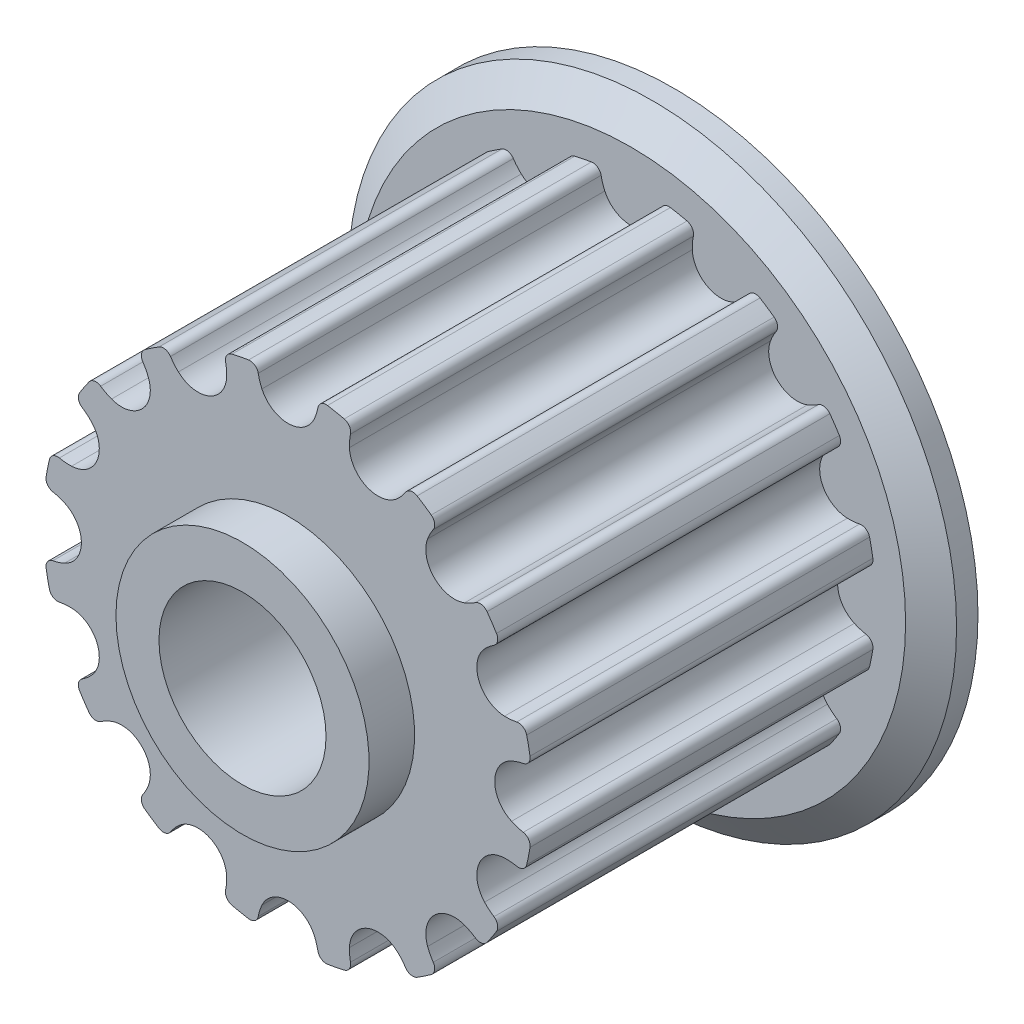
SolidWorks part; units mm, degrees
ref_plane "Front Plane" through (0, 0, 0) normal (0, 0, 1) x (1, 0, 0)
ref_plane "Top Plane" through (0, 0, 0) normal (0, 1, 0) x (1, 0, 0)
ref_plane "Right Plane" through (0, 0, 0) normal (1, 0, 0) x (0, 0, -1)
sketch "Sketch1" plane through (0, 0, 0) normal (0, 0, 1) x (1, 0, 0)
  line L1 (-2.553, 6.1245) -> (2.553, 6.1245) construction
  line L4 (0, 0) -> (0, 6.1245) construction
  line L5 (0, 6.1245) -> (0, 12.0665) construction
  line L6 (0, 7.6455) -> (2.9417, 7.0569) construction
  line L7 (2.9417, 7.0569) -> (3.8741, 6.6682) construction
  line L8 (2.9417, 7.0569) -> (2.553, 6.1245) construction
  line L9 (-2.9417, 7.0569) -> (-2.553, 6.1245) construction
  line L10 (-2.7951, 6.7052) -> (-3.7579, 9.015)
  line L11 (-3.7579, 9.015) -> (3.7579, 9.015)
  line L12 (3.7579, 9.015) -> (2.7951, 6.7052)
  circle A0 centre (0, 0) radius 7.6455 construction
  circle A1 centre (0, 0) radius 9.015 construction
  circle A2 centre (0, 0) radius 7.2645 construction
  arc A3 (-0.7739, 6.6229) -> (0.7739, 6.6229) centre (0, 6.9745) ccw
  arc A4 (-0.7739, 6.6229) -> (-0.8836, 6.9694) centre (0.61, 7.2516) cw
  arc A5 (-2.7951, 6.7052) -> (-1.1695, 7.1697) centre (0, 0) cw
  arc A6 (-0.8836, 6.9694) -> (-1.1695, 7.1697) centre (-1.1292, 6.923) ccw
  arc A7 (2.7951, 6.7052) -> (1.1695, 7.1697) centre (0, 0) ccw
  arc A8 (0.8836, 6.9694) -> (1.1695, 7.1697) centre (1.1292, 6.923) cw
  arc A9 (0.7739, 6.6229) -> (0.8836, 6.9694) centre (-0.61, 7.2516) ccw
  point P6 (0, 20.9083)
  point P11 (0, 7.6455)
  point P13 (0, 9.015)
  point P14 (0, 7.2645)
  dimension "D1" = 8.8419
  dimension "D2" = 4.421
sketch "Sketch2" plane through (0, 0, 0) normal (1, 0, 0) x (0, 0, -1)
  line L0 (-8.775, 2.3812) -> (8.775, 2.3812)
  line L1 (-8.775, 2.3812) -> (-8.775, 9.015)
  line L2 (-3.29, 9.015) -> (-8.775, 9.015)
  line L3 (-3.925, 2.3813) -> (-3.925, 9.015) construction
  line L4 (-3.925, 9.015) -> (-2.655, 9.015) construction
  line L5 (-2.655, 9.015) -> (-2.655, 7.2645) construction
  line L6 (-2.655, 7.2645) -> (7.505, 7.2645)
  line L7 (7.505, 7.2645) -> (7.505, 9.015) construction
  line L8 (7.505, 9.015) -> (8.775, 9.015) construction
  line L9 (8.775, 9.015) -> (8.775, 2.3812)
  line L10 (-8.775, 0) -> (8.775, 0) construction
  line L11 (8.14, 9.015) -> (7.505, 8.1398)
  line L12 (-2.655, 8.1398) -> (-3.29, 9.015)
  line L14 (-2.655, 8.1398) -> (-2.655, 7.2645)
  line L15 (7.505, 7.2645) -> (7.505, 8.1398)
  line L16 (8.14, 9.015) -> (8.775, 9.015)
  arc A0 (-2.655, 8.1398) -> (-3.29, 9.015) centre (-3.5757, 8.1398) ccw construction
  arc A1 (7.505, 8.1398) -> (8.14, 9.015) centre (8.4257, 8.1398) cw construction
  point P12 (-2.655, 8.1398)
  point P14 (-3.29, 9.015)
  point P20 (7.505, 8.1398)
  point P21 (8.14, 9.015)
  point P25 (7.505, 0)
  point P26 (-2.655, 0)
  dimension "OA" = 17.55
  dimension "Bore" = 4.7625
  dimension "Outside Width" = 11.43
  dimension "Inside Width" = 10.16
revolve "Revolve1" add sketch "Sketch2" angle 360 mid plane about L10
sketch "Sketch3" plane through (0, 0, 0) normal (0, 0, 1) x (1, 0, 0)
  line L6 (3.7579, 9.015) -> (-3.7579, 9.015)
  line L7 (2.7951, 6.7052) -> (3.7579, 9.015)
  line L8 (-3.7579, 9.015) -> (-2.7951, 6.7052)
  line L9 (3.7579, 9.015) -> (-3.7579, 9.015)
  line L10 (2.7951, 6.7052) -> (3.7579, 9.015)
  line L11 (-3.7579, 9.015) -> (-2.7951, 6.7052)
  arc A8 (2.7951, 6.7052) -> (1.1695, 7.1697) centre (0, 0) ccw
  arc A9 (1.1695, 7.1697) -> (0.8836, 6.9694) centre (1.1292, 6.923) ccw
  arc A10 (0.7739, 6.6229) -> (0.8836, 6.9694) centre (-0.61, 7.2516) ccw
  arc A11 (-0.7739, 6.6229) -> (0.7739, 6.6229) centre (0, 6.9745) ccw
  arc A12 (-0.8836, 6.9694) -> (-0.7739, 6.6229) centre (0.61, 7.2516) ccw
  arc A13 (-0.8836, 6.9694) -> (-1.1695, 7.1697) centre (-1.1292, 6.923) ccw
  arc A14 (-1.1695, 7.1697) -> (-2.7951, 6.7052) centre (0, 0) ccw
  arc A15 (2.7951, 6.7052) -> (1.1695, 7.1697) centre (0, 0) ccw
  arc A16 (1.1695, 7.1697) -> (0.8836, 6.9694) centre (1.1292, 6.923) ccw
  arc A17 (0.7739, 6.6229) -> (0.8836, 6.9694) centre (-0.61, 7.2516) ccw
  arc A18 (-0.7739, 6.6229) -> (0.7739, 6.6229) centre (0, 6.9745) ccw
  arc A19 (-0.8836, 6.9694) -> (-0.7739, 6.6229) centre (0.61, 7.2516) ccw
  arc A20 (-0.8836, 6.9694) -> (-1.1695, 7.1697) centre (-1.1292, 6.923) ccw
  arc A21 (-1.1695, 7.1697) -> (-2.7951, 6.7052) centre (0, 0) ccw
  dimension "D1" = 0
extrude "Cut-Extrude1" cut sketch "Sketch3" against normal up to vertex (7.505 mm away) from vertex up to point (0, 7.2645, -7.505) starting at point (0, 7.2645, 2.655)
pattern_circular "CirPattern1" count 16 over 360 about axis through (0, 0, 8.775) along (0, 0, 1) of "Cut-Extrude1"
sketch "Sketch4" plane through (0, 0, 0) normal (1, 0, 0) x (0, -1, 0)
  line L0 (0, -2.655) -> (0, -8.775) construction
  line L1 (-2.3812, -8.775) -> (2.3812, -8.775) construction
  line L2 (8.1398, -2.655) -> (-8.1398, -2.655) construction
  circle A0 centre (0, -5.715) radius 1.7526
extrude "Cut-Extrude2" cut sketch "Sketch4" along normal through all
ref_plane "Plane1" through (0, 0, 5.715) normal (0, 0, 1) x (1, 0, 0)
sketch "Sketch5" plane through (0, 0, 5.715) normal (0, 0, 1) x (1, 0, 0)
  line L0 (0, 0) -> (0, 9.015) construction
  line L1 (2.3812, -1.3716) -> (2.3812, 0)
  line L2 (2.7622, -1.7526) -> (8.462, -1.7526)
  line L3 (2.3812, 0) -> (9.015, 0) construction
  line L4 (2.3812, 0) -> (8.843, 0)
  line L5 (8.843, 0) -> (8.843, -1.3716)
  line L6 (2.7622, -1.7526) -> (2.3812, -1.3716)
  line L7 (8.843, -1.3716) -> (8.462, -1.7526)
  circle A0 centre (0, 0) radius 9.015 construction
  circle A1 centre (0, 0) radius 2.3812 construction
  point P2 (2.3812, -1.7526)
  point P11 (8.843, -1.7526)
revolve "Revolve2" add sketch "Sketch5" angle 360 mid plane about L4
sketch "Sketch6" plane through (8.843, 5.3841, 0) normal (-1, 0, 0) x (0, -1, 0)
  line L1 (5.3841, 6.7269) -> (4.5078, 6.2209)
  line L2 (4.5078, 6.2209) -> (4.5078, 5.2091)
  line L3 (4.5078, 5.2091) -> (5.3841, 4.7031)
  line L4 (5.3841, 4.7031) -> (6.2604, 5.2091)
  line L5 (6.2604, 5.2091) -> (6.2604, 6.2209)
  line L6 (6.2604, 6.2209) -> (5.3841, 6.7269)
  circle A0 centre (5.3841, 5.715) radius 0.8763 construction
  dimension "D1" = 1.7526
extrude "Cut-Extrude3" cut sketch "Sketch6" along normal blind 1.3144
pattern_circular "CirPattern3" count 2 over 90 about axis through (0, 0, 8.775) along (0, 0, 1) of "Cut-Extrude2", "Revolve2", "Cut-Extrude3"
chamfer "Chamfer1" distance 0.2807 angle 45 2 edges at (2.3812, 0, 8.775) (9.015, 0, 8.775)
ref_axis "Center Axis 1" through (0, 0, -8.775) along (0, 0, 1)
ref_plane "Contact Plane 1" through (0, 0, 8.775) normal (0, 0, 1) x (1, 0, 0)
ref_plane "Contact Plane 2" through (0, 0, -8.775) normal (0, 0, -1) x (-1, 0, 0)
sketch "Sketch7" plane through (0, 0, 8.775) normal (0, 0, 1) x (1, 0, 0)
  circle A0 centre (0, 0) radius 9.015 construction
  circle A1 centre (0, 0) radius 9.015
extrude "Cut-Extrude4" cut sketch "Sketch7" against normal up to surface (6.12 mm away)
sketch "Sketch8" plane through (0, 0, -8.775) normal (0, 0, -1) x (-1, 0, 0)
  circle A0 centre (0, 0) radius 2.475
  dimension "D1" = 4.95
extrude "Cut-Extrude5" cut sketch "Sketch8" against normal through all
sketch "Sketch9" plane through (0, 0, 2.655) normal (0, 0, 1) x (1, 0, 0)
  circle A0 centre (0, 0) radius 2.475 construction
  circle A1 centre (0, 0) radius 2.475
  circle A2 centre (0, 0) radius 3.75
  dimension "D1" = 7.5
extrude "Boss-Extrude1" add sketch "Sketch9" along normal blind 1.35
equation "\"D2@Sketch1\"= \"D1@Sketch1\" / 2"
equation "\"D1@Sketch6\" = \"Set Screw@Sketch4\" / 2"
equation "\"D1@Cut-Extrude3\" = \"D1@Sketch6\"*.75"
